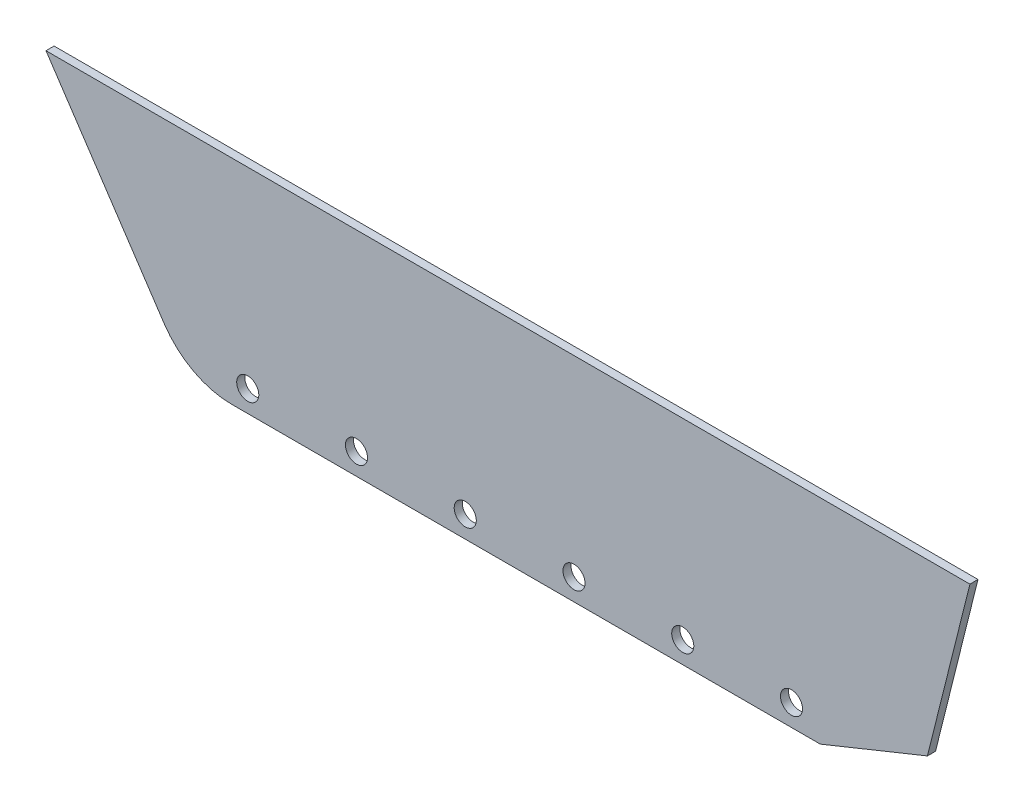
SolidWorks part; units mm, degrees
material "5052-H34"
ref_plane "Front Plane" through (0, 0, 0) normal (0, 0, 1) x (1, 0, 0)
ref_plane "Top Plane" through (0, 0, 0) normal (0, 1, 0) x (1, 0, 0)
ref_plane "Right Plane" through (0, 0, 0) normal (1, 0, 0) x (0, 0, -1)
sketch "Sketch1" plane through (0, 0, 0) normal (0, 0, 1) x (1, 0, 0)
  line L3 (428.1206, 28.9396) -> (0.5404, 28.9396)
  line L6 (-98.8794, 3.851) -> (-31.8794, -96.649)
  line L7 (428.1206, 28.9396) -> (403.1206, -71.149)
  line L9 (403.1206, -71.149) -> (366, -96.649)
  line L10 (-31.8794, -96.649) -> (366, -96.649)
  line L11 (0.5404, 28.9396) -> (-115.6052, 28.9396)
  line L12 (-98.8794, 3.851) -> (-115.6052, 28.9396)
  circle A0 centre (3.1206, -83.899) radius 6.5
  circle A1 centre (67.1206, -83.899) radius 6.5
  circle A2 centre (131.1206, -83.899) radius 6.5
  circle A3 centre (195.1206, -83.899) radius 6.5
  circle A4 centre (259.1206, -83.899) radius 6.5
  circle A5 centre (323.1206, -83.899) radius 6.5
  point P0 (-48.8794, -71.149)
  point P2 (-31.8794, -96.649)
  point P8 (48, -83.899)
  point P9 (403.1206, -71.149)
  dimension "D2" = 64
  dimension "D4" = 64
  dimension "D1" = 25.5
  dimension "D3" = 75
  dimension "D5" = 25
  dimension "D6" = 80
  dimension "D7" = 527
  dimension "D8" = 180
  dimension "D9" = 64
  dimension "D10" = 64
  dimension "D11" = 64
  dimension "D12" = 123.69
  dimension "D13" = 12.75
extrude "Boss-Extrude1" add sketch "Sketch1" along normal blind 4.7625 contours L3 L11 L12 L6 L10 L9 L7
extrude "Cut-Extrude1" cut sketch "Sketch1<4>" along normal through all contours A0 | A1 | A2 | A3 | A4 | A5 region at (3.1206, -83.899, 0)
sketch "Sketch1<4>" plane through (0, 0, 0) normal (0, 0, 1) x (1, 0, 0) same geometry as "Sketch1"
sketch "Sketch2" plane through (0, 0, 0) normal (0, 0, -1) x (-1, 0, 0)
  circle A0 centre (-291.1206, -83.899) radius 6.5
  circle A2 centre (-241.5603, -124.3932) radius 6.5
  circle A3 centre (-192, -83.899) radius 6.5
  circle A4 centre (-128, -83.899) radius 6.5
  circle A5 centre (-64, -83.899) radius 6.5
  circle A6 centre (0, -83.899) radius 6.5
  dimension "D2" = 0
  dimension "D3" = 64
  dimension "D4" = 64
  dimension "D5" = 64
  dimension "D6" = 64
  dimension "D7" = 64
  dimension "D1" = 32
sketch "Sketch5" plane through (0, 0, 0) normal (0, 0, -1) x (-1, 0, 0)
  line L0 (48.8794, -71.149) -> (-14.2353, -96.649)
  line L1 (31.8794, -96.649) -> (-366, -96.649) construction
  line L2 (-14.2353, -96.649) -> (31.8794, -96.649)
  line L3 (31.8794, -96.649) -> (48.8794, -71.149)
  line L6 (-366, -96.649) -> (-403.1206, -71.149)
  line L7 (-403.1206, -71.149) -> (-352, -71.149)
  line L9 (-352, -71.149) -> (-326.5, -96.649)
  line L11 (-366, -96.649) -> (-326.5, -96.649)
  dimension "D1" = 22
  dimension "D2" = 45
extrude "Cut-Extrude2" [suppressed] cut sketch "Sketch5" against normal up to next
sketch "Sketch6" plane through (0, 0, 4.7625) normal (0, 0, 1) x (1, 0, 0)
  line L0 (-48.8794, -71.149) -> (14.2353, -96.649)
  line L1 (-31.8794, -96.649) -> (366, -96.649) construction
  line L2 (14.2353, -96.649) -> (-31.8794, -96.649)
  line L3 (-31.8794, -96.649) -> (-48.8794, -71.149)
  dimension "D1" = 158
fillet "Fillet1" radius 48 1 edges at (-31.8794, -96.649, 2.3813)
sketch "Sketch7" plane through (0, 0, 4.7625) normal (0, 0, 1) x (1, 0, 0)
  line L0 (403.1206, -71.149) -> (340.0059, -96.649)
  line L1 (-31.8794, -96.649) -> (366, -96.649) construction
  line L2 (340.0059, -96.649) -> (366, -96.649)
  line L3 (366, -96.649) -> (403.1206, -71.149)
  dimension "D1" = 22
extrude "Cut-Extrude3" cut sketch "Sketch7" against normal blind 10
sketch "Sketch9" plane through (0, 0, 0) normal (0, 0, -1) x (-1, 0, 0)
  line L0 (-403.1206, -71.149) -> (48.8794, -71.149)
  line L1 (48.8794, -71.149) -> (48.8794, -114.9143)
  line L2 (48.8794, -114.9143) -> (-403.1206, -114.9143)
  line L3 (-403.1206, -114.9143) -> (-403.1206, -71.149)
extrude "Cut-Extrude4" [suppressed] cut sketch "Sketch9" against normal blind 10
